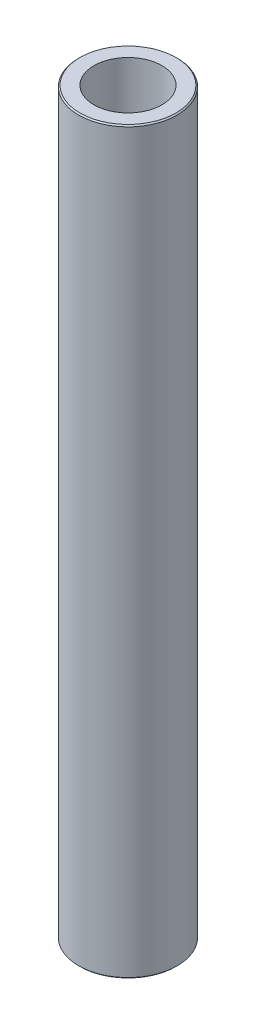
SolidWorks part; units mm, degrees
ref_plane "Front Plane" through (0, 0, 0) normal (0, 0, 1) x (1, 0, 0)
ref_plane "Top Plane" through (0, 0, 0) normal (0, 1, 0) x (1, 0, 0)
ref_plane "Right Plane" through (0, 0, 0) normal (1, 0, 0) x (0, 0, -1)
sketch "Sketch1" plane through (0, 0, 0) normal (0, 1, 0) x (1, 0, 0)
  circle A0 centre (0, 0) radius 40
  dimension "SHAFT_OD" = 80
extrude "Boss-Extrude1" add sketch "Sketch1" along normal blind 600
sketch "Sketch2" plane through (0, 0, 0) normal (0, 1, 0) x (1, 0, 0)
  circle A0 centre (0, 0) radius 27.5936
  dimension "BORE_D" = 55.1873
extrude "Cut-Extrude1" cut sketch "Sketch2" along normal through all
chamfer "Chamfer1" distance 0.9942 angle 45 2 edges at (0, 600, 40) (0, 0, 40)
